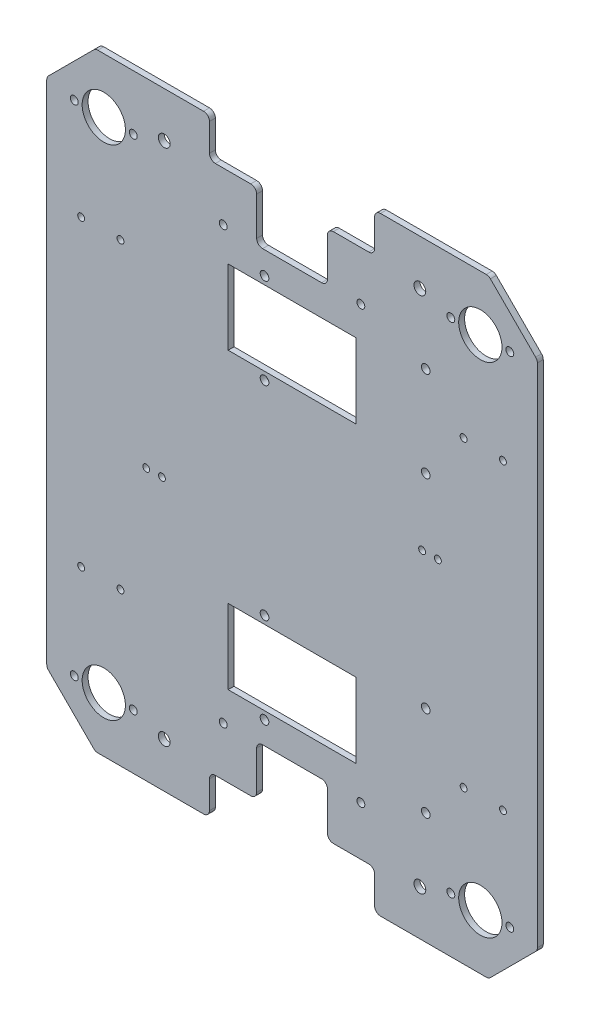
SolidWorks part; units mm, degrees
material "Alliage 1060"
ref_plane "Plan de dessus" through (0, 0, 0) normal (0, 0, 1) x (1, 0, 0)
ref_plane "Plan de droite" through (0, 0, 0) normal (0, 1, 0) x (1, 0, 0)
ref_plane "Plan de face" through (0, 0, 0) normal (1, 0, 0) x (0, 0, -1)
sketch "Esquisse1" plane through (0, 0, 0) normal (0, 0, 1) x (1, 0, 0)
  line L0 (0, 0) -> (-200, 0)
  line L1 (-200, 0) -> (-224.7487, 24.7487)
  line L2 (-224.7487, 24.7487) -> (-224.7487, 284.7487)
  line L3 (-224.7487, 284.7487) -> (-200, 309.4975)
  line L4 (-200, 309.4975) -> (0, 309.4975)
  line L5 (0, 309.4975) -> (24.7487, 284.7487)
  line L6 (24.7487, 284.7487) -> (24.7487, 24.7487)
  line L7 (24.7487, 24.7487) -> (0, 0)
  dimension "D1" = 260
  dimension "D2" = 35
  dimension "D3" = 135
  dimension "D4" = 200
extrude "Base" add sketch "Esquisse1" along normal blind 3
sketch "Esquisse3" plane through (0, 0, 0) normal (0, 0, -1) x (-1, 0, 0)
  line L0 (142, 0) -> (142, 20)
  line L1 (200, 0) -> (0, 0) construction
  line L2 (142, 20) -> (118, 20)
  line L3 (118, 20) -> (118, 45.5)
  line L4 (118, 45.5) -> (82, 45.5)
  line L5 (82, 45.5) -> (82, 20)
  line L6 (82, 20) -> (58, 20)
  line L7 (58, 20) -> (58, 0)
  line L8 (-24.7487, 154.7487) -> (224.7487, 154.7487) construction
  line L9 (-24.7487, 24.7487) -> (-24.7487, 284.7487) construction
  line L10 (224.7487, 284.7487) -> (224.7487, 24.7487) construction
  line L11 (58, 0) -> (142, 0)
  line L12 (58, 309.4975) -> (142, 309.4975)
  line L13 (142, 309.4975) -> (142, 289.4975)
  line L14 (142, 289.4975) -> (118, 289.4975)
  line L15 (118, 289.4975) -> (118, 263.9975)
  line L16 (118, 263.9975) -> (82, 263.9975)
  line L17 (82, 263.9975) -> (82, 289.4975)
  line L18 (82, 289.4975) -> (58, 289.4975)
  line L19 (58, 289.4975) -> (58, 309.4975)
  line L20 (100, 45.5) -> (100, -49954.5) construction
  line L21 (0, 309.4975) -> (200, 309.4975) construction
  line L22 (67.5, 244.4975) -> (132.5, 244.4975)
  line L23 (67.5, 244.4975) -> (67.5, 214.4975)
  line L24 (67.5, 214.4975) -> (132.5, 214.4975)
  line L25 (132.5, 244.4975) -> (132.5, 214.4975)
  line L26 (132.5, 65) -> (132.5, 95)
  line L27 (67.5, 95) -> (132.5, 95)
  line L28 (67.5, 65) -> (132.5, 65)
  line L29 (67.5, 65) -> (67.5, 95)
  circle A0 centre (65, 45) radius 2
  circle A1 centre (135, 45) radius 2
  circle A2 centre (135, 264.4975) radius 2
  circle A3 centre (65, 264.4975) radius 2
  point P4 (100, 45.5)
  point P11 (100, 0)
  point P40 (100, 244.4975)
  point P41 (132.5, 229.4975)
  dimension "D7" = 4
  dimension "D5" = 25
  dimension "D1" = 20
  dimension "D2" = 24
  dimension "D3" = 36
  dimension "D4" = 25.5
  dimension "D6" = 7
  dimension "D8" = 80
  dimension "D9" = 30
  dimension "D10" = 65
extrude "Perçage roues encodeuses" cut sketch "Esquisse3" against normal through all
fillet "Congé1" radius 3 24 edges at (-224.7487, 24.7487, 1.5) (24.7487, 24.7487, 1.5) (0, 0, 1.5) (-142, 20, 1.5) (-118, 45.5, 1.5) (-118, 20, 1.5) (-200, 0, 1.5) (-142, 0, 1.5) (-82, 45.5, 1.5) (-58, 20, 1.5) (-82, 20, 1.5) (-58, 0, 1.5) (24.7487, 284.7487, 1.5) (-142, 289.4975, 1.5) (-118, 263.9975, 1.5) (-224.7487, 284.7487, 1.5) (-200, 309.4975, 1.5) (-142, 309.4975, 1.5) (-118, 289.4975, 1.5) (-82, 263.9975, 1.5) (-58, 289.4975, 1.5) (-82, 289.4975, 1.5) (-58, 309.4975, 1.5) (0, 309.4975, 1.5)
sketch "Esquisse6" plane through (0, 0, 3) normal (0, 0, 1) x (1, 0, 0)
  line L0 (-195.7487, 28) -> (-210.7487, 28) construction
  line L1 (-195.7487, 28) -> (-180.7487, 28) construction
  line L2 (-100, 231.5685) -> (-100, -49768.4315) construction
  line L4 (-67.5, 214.4975) -> (-132.5, 214.4975) construction
  line L5 (-203.2843, 154.7487) -> (49796.7157, 154.7487) construction
  line L6 (-224.7487, 283.5061) -> (-224.7487, 25.9914) construction
  line L15 (-198.7574, 0) -> (-145, 0) construction
  circle A25 centre (-180.7487, 28) radius 2
  circle A26 centre (-210.7487, 28) radius 2
  circle A27 centre (-195.7487, 28) radius 11
  circle A31 centre (-19.2513, 28) radius 2
  circle A32 centre (10.7487, 28) radius 2
  circle A33 centre (-4.2513, 28) radius 11
  circle A34 centre (-4.2513, 281.4975) radius 11
  circle A35 centre (10.7487, 281.4975) radius 2
  circle A36 centre (-19.2513, 281.4975) radius 2
  circle A37 centre (-195.7487, 281.4975) radius 11
  circle A38 centre (-210.7487, 281.4975) radius 2
  circle A39 centre (-180.7487, 281.4975) radius 2
  point P15 (-100, 214.4975)
  point P20 (-224.7487, 154.7487)
  dimension "D2" = 4
  dimension "D3" = 15
  dimension "D4" = 15
  dimension "D5" = 180
  dimension "D9" = 29
  dimension "D13" = 22
  dimension "D15" = 28
extrude "Perçage billes porteuses" cut sketch "Esquisse6" against normal up to next
sketch "Esquisse8" plane through (0, 0, 3) normal (0, 0, 1) x (1, 0, 0)
  line L0 (-100, 263.9975) -> (-100, 95) construction
  line L1 (-85, 263.9975) -> (-115, 263.9975) construction
  line L2 (-132.5, 95) -> (-67.5, 95) construction
  line L3 (-145, 309.4975) -> (-198.7574, 309.4975) construction
  line L4 (-142, 292.4975) -> (-142, 306.4975) construction
  line L5 (-198.7574, 0) -> (-145, 0) construction
  line L6 (-142, 3) -> (-142, 17) construction
  circle A0 centre (-165, 23) radius 3
  circle A1 centre (-165, 286.4975) radius 3
  circle A2 centre (-35, 286.4975) radius 3
  circle A3 centre (-35, 23) radius 3
  dimension "D1" = 23
  dimension "D2" = 23
  dimension "D3" = 6
  dimension "D4" = 23
  dimension "D5" = 23
  dimension "D6" = 6
extrude "Perçage profilés" cut sketch "Esquisse8" against normal up to next
sketch "Esquisse10" plane through (0, 0, 3) normal (0, 0, 1) x (1, 0, 0)
  line L0 (-224.7487, 283.5061) -> (-224.7487, 25.9914) construction
  line L1 (-100, 214.4975) -> (-100, 95) construction
  line L2 (-123.75, 179.6975) -> (-100, 179.6975) construction
  line L3 (-67.5, 214.4975) -> (-132.5, 214.4975) construction
  line L4 (-100, 179.6975) -> (21.8665, 179.6975) construction
  line L5 (-224.7487, 154.7487) -> (24.7487, 154.7487) construction
  line L6 (24.7487, 25.9914) -> (24.7487, 283.5061) construction
  line L7 (-132.5, 95) -> (-67.5, 95) construction
  line L8 (-158.75, 179.6975) -> (-123.75, 179.6975) construction
  line L9 (-132.5, 229.4975) -> (-67.5, 229.4975) construction
  line L10 (-132.5, 214.4975) -> (-132.5, 244.4975) construction
  line L11 (-67.5, 244.4975) -> (-67.5, 214.4975) construction
  line L12 (-100, 129.8) -> (-139.6239, 129.8) construction
  line L13 (-100, 129.8) -> (10.2968, 129.8) construction
  circle A8 centre (-123.75, 179.6975) radius 1.75
  circle A9 centre (-120, 208.4975) radius 1.75
  circle A10 centre (-158.75, 179.6975) radius 1.75
  circle A11 centre (-80, 208.4975) radius 1.75
  circle A18 centre (-80, 101) radius 1.75
  circle A19 centre (-120, 101) radius 1.75
  circle A20 centre (-71.75, 179.6975) radius 1.75
  circle A21 centre (-40.75, 179.6975) radius 1.75
  circle A22 centre (-128.25, 129.8) radius 1.75
  circle A23 centre (-159.25, 129.8) radius 1.75
  circle A24 centre (-76.25, 129.8) radius 1.75
  circle A25 centre (-41.25, 129.8) radius 1.75
  dimension "D1" = 3.5
  dimension "D2" = 23.75
  dimension "D3" = 20
  dimension "D4" = 3.5
  dimension "D5" = 3.5
  dimension "D6" = 35
  dimension "D7" = 21
  dimension "D8" = 28.8
  dimension "D9" = 3.5
  dimension "D10" = 3.5
  dimension "D12" = 31
  dimension "D13" = 28.8
  dimension "D14" = 3.5
  dimension "D15" = 3.5
  dimension "D16" = 3.5
  dimension "D17" = 3.5
  dimension "D18" = 28.25
  dimension "D19" = 31
  dimension "D21" = 35
  dimension "D11" = 28.25
  dimension "D20" = 23.75
sketch "Esquisse15" plane through (0, 0, 0) normal (0, 0, -1) x (-1, 0, 0)
  line L0 (114, 103) -> (32, 103) construction
  line L1 (-24.7487, 154.7487) -> (23.202, 154.7487) construction
  line L2 (-24.7487, 25.9914) -> (-24.7487, 283.5061) construction
  line L3 (100, 95) -> (100, 134.4542) construction
  line L4 (132.5, 95) -> (67.5, 95) construction
  line L5 (0, 80) -> (59.1109, 80) construction
  line L6 (55, 0) -> (1.2426, 0) construction
  circle A0 centre (114, 103) radius 2.2
  circle A1 centre (32, 103) radius 2.2
  circle A2 centre (114, 57) radius 2.2
  circle A3 centre (32, 57) radius 2.2
  circle A4 centre (32, 252.4975) radius 2.2
  circle A5 centre (114, 252.4975) radius 2.2
  circle A6 centre (114, 206.4975) radius 2.2
  circle A7 centre (32, 206.4975) radius 2.2
  dimension "D2" = 4.4
  dimension "D1" = 82
  dimension "D3" = 80
  dimension "D4" = 23
  dimension "D5" = 14
extrude "Perçage bloc moteur" cut sketch "Esquisse15" against normal up to surface (3 mm away) up to face at (-38, 23, 3)
sketch "Esquisse16" plane through (0, 0, 0) normal (0, 0, -1) x (-1, 0, 0)
  line L0 (224.7487, 154.7487) -> (-24.7487, 154.7487) construction
  line L1 (67.5, 61) -> (132.5, 61)
  line L2 (67.5, 61) -> (67.5, 99)
  line L3 (67.5, 99) -> (132.5, 99)
  line L4 (132.5, 61) -> (132.5, 99)
  line L5 (224.7487, 283.5061) -> (224.7487, 25.9914) construction
  line L6 (-24.7487, 25.9914) -> (-24.7487, 283.5061) construction
  line L7 (100, 309.4975) -> (100, 0) construction
  line L8 (100, 0) -> (55, 0) construction
  line L9 (67.5, 210.4975) -> (132.5, 210.4975)
  line L10 (132.5, 248.4975) -> (132.5, 210.4975)
  line L11 (67.5, 248.4975) -> (132.5, 248.4975)
  line L12 (67.5, 248.4975) -> (67.5, 210.4975)
  line L13 (198.7574, 0) -> (145, 0) construction
  point P10 (132.5, 80)
  point P13 (100, 154.7487)
  point P16 (100, 61)
  dimension "D1" = 80
  dimension "D2" = 38
  dimension "D3" = 65
extrude "Enlèv. mat.-Extru.1" cut sketch "Esquisse16" against normal through all
sketch "Esquisse14" plane through (0, 309.4975, 0) normal (0, 1, 0) x (1, 0, 0)
  line L0 (-100, -3) -> (-100, 0) construction
  line L1 (-85, -3) -> (-115, -3) construction
  line L2 (-85, 0) -> (-115, 0) construction
sketch "Esquisse18" plane through (0, 0, 0) normal (0, 0, -1) x (-1, 0, 0)
  line L0 (224.7487, 154.7487) -> (-24.7487, 154.7487) construction
  line L1 (224.7487, 283.5061) -> (224.7487, 25.9914) construction
  line L2 (-24.7487, 25.9914) -> (-24.7487, 283.5061) construction
  line L3 (100, 0) -> (100, 309.4975) construction
  line L4 (197.2487, 231.2487) -> (197.2487, 78.2487) construction
  line L5 (201.2487, 78.2487) -> (193.2487, 78.2487)
  circle A0 centre (201.2487, 78.2487) radius 1.65
  circle A1 centre (193.2487, 78.2487) radius 1.65
  circle A2 centre (193.2487, 231.2487) radius 1.65
  circle A3 centre (201.2487, 231.2487) radius 1.65
  circle A4 centre (-1.2487, 231.2487) radius 1.65
  circle A5 centre (6.7513, 231.2487) radius 1.65
  circle A6 centre (-1.2487, 78.2487) radius 1.65
  circle A7 centre (6.7513, 78.2487) radius 1.65
  point P8 (100, 154.7487)
  point P12 (197.2487, 154.7487)
  point P15 (197.2487, 78.2487)
  dimension "D2" = 3.3
  dimension "D1" = 153
  dimension "D3" = 8
  dimension "D4" = 27.5
sketch "Esquisse17" plane through (0, 0, 0) normal (0, 0, -1) x (-1, 0, 0)
  line L0 (-24.7487, 154.7487) -> (224.7487, 154.7487) construction
  line L1 (-24.7487, 25.9914) -> (-24.7487, 283.5061) construction
  line L2 (224.7487, 283.5061) -> (224.7487, 25.9914) construction
  line L3 (192.7487, 78.2487) -> (192.7487, 231.2487) construction
  line L4 (186.7487, 231.2487) -> (198.7487, 231.2487) construction
  line L5 (100, 309.4975) -> (100, 0) construction
  circle A0 centre (198.7487, 231.2487) radius 2
  circle A1 centre (186.7487, 231.2487) radius 2
  circle A2 centre (198.7487, 78.2487) radius 2
  circle A3 centre (186.7487, 78.2487) radius 2
  circle A4 centre (1.2513, 78.2487) radius 2
  circle A5 centre (13.2513, 78.2487) radius 2
  circle A6 centre (13.2513, 231.2487) radius 2
  circle A7 centre (1.2513, 231.2487) radius 2
  point P9 (192.7487, 154.7487)
  point P12 (192.7487, 231.2487)
  point P21 (100, 154.7487)
  dimension "D3" = 4
  dimension "D1" = 153
  dimension "D2" = 12
  dimension "D4" = 32
sketch "Esquisse19" plane through (0, 0, 0) normal (0, 0, -1) x (-1, 0, 0)
  line L0 (-24.7487, 154.7487) -> (224.7487, 154.7487) construction
  line L1 (-24.7487, 25.9914) -> (-24.7487, 283.5061) construction
  line L2 (224.7487, 283.5061) -> (224.7487, 25.9914) construction
  line L3 (100, 0.2054) -> (100, 309.292) construction
  line L4 (-7.2487, 231.7487) -> (12.7513, 231.7487) construction
  line L5 (25.8513, 171.6987) -> (33.8513, 171.6987) construction
  line L6 (166.1487, 137.7987) -> (174.1487, 137.7987) construction
  circle A0 centre (166.1487, 137.7987) radius 1.75
  circle A1 centre (174.1487, 137.7987) radius 1.75
  circle A8 centre (-7.2487, 231.7487) radius 1.75
  circle A9 centre (12.7513, 231.7487) radius 1.75
  circle A11 centre (12.7513, 77.7487) radius 1.75
  circle A13 centre (-7.2487, 77.7487) radius 1.75
  circle A15 centre (187.2487, 77.7487) radius 1.75
  circle A17 centre (207.2487, 77.7487) radius 1.75
  circle A19 centre (207.2487, 231.7487) radius 1.75
  circle A21 centre (187.2487, 231.7487) radius 1.75
  circle A23 centre (25.8513, 171.6987) radius 1.75
  circle A25 centre (33.8513, 171.6987) radius 1.75
  point P33 (100, 154.7487)
  point P36 (100, 154.7487)
  dimension "D11" = 3.5
  dimension "D9" = 77
  dimension "D10" = 17.5
  dimension "D2" = 20
  dimension "D3" = 16.95
  dimension "D4" = 50.6
  dimension "D5" = 8
  dimension "D6" = 2
extrude "Perçage actionneur Main_De_Dieu" cut sketch "Esquisse19" against normal through all
